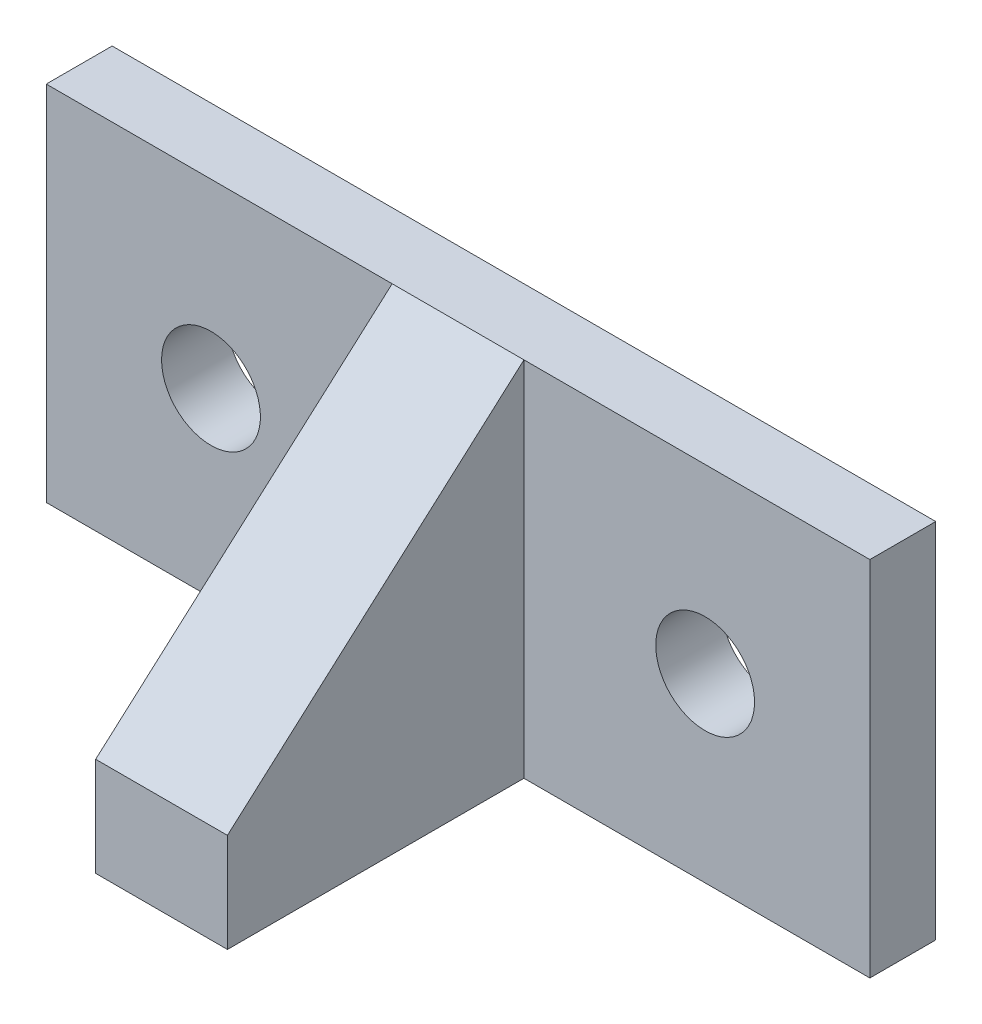
SolidWorks part; units mm, degrees
ref_plane "Front Plane" through (0, 0, 0) normal (0, 0, 1) x (1, 0, 0)
ref_plane "Top Plane" through (0, 0, 0) normal (0, 1, 0) x (1, 0, 0)
ref_plane "Right Plane" through (0, 0, 0) normal (1, 0, 0) x (0, 0, -1)
sketch "Sketch1" plane through (0, 0, 0) normal (1, 0, 0) x (0, 0, -1)
  line L0 (0, 55) -> (-45, 15)
  line L1 (0, 0) -> (10, 0)
  line L2 (0, 0) -> (0, 55)
  line L3 (0, 55) -> (10, 55)
  line L4 (10, 0) -> (10, 55)
  line L5 (-45, 15) -> (-45, 0)
  line L6 (55, 0) -> (-55, 0) construction
  line L7 (-45, 0) -> (0, 0)
  dimension "D1" = 10
  dimension "D2" = 55
  dimension "D3" = 15
  dimension "D4" = 55
extrude "Boss-Extrude1" add sketch "Sketch1" along normal mid plane 125 contours L1 L4 L3 L2 region at (0, 27.5, -5)
extrude "Boss-Extrude2" add sketch "Sketch1<3>" along normal mid plane 20 contours L5 L7 L2 L0 region at (0, 19.4048, 18.2143)
sketch "Sketch1<3>" plane through (0, 0, 0) normal (1, 0, 0) x (0, 0, -1) same geometry as "Sketch1"
sketch "Sketch2" plane through (0, 0, 0) normal (0, 0, 1) x (1, 0, 0)
  circle A0 centre (37.5, 27.5) radius 7.5
  dimension "D2" = 15
  dimension "D1" = 37.5
  dimension "D3" = 27.5
extrude "Cut-Extrude1" cut sketch "Sketch2" against normal blind 10
mirror "Mirror1" about plane through (0, 0, 0) normal (1, 0, 0) of "Cut-Extrude1"
